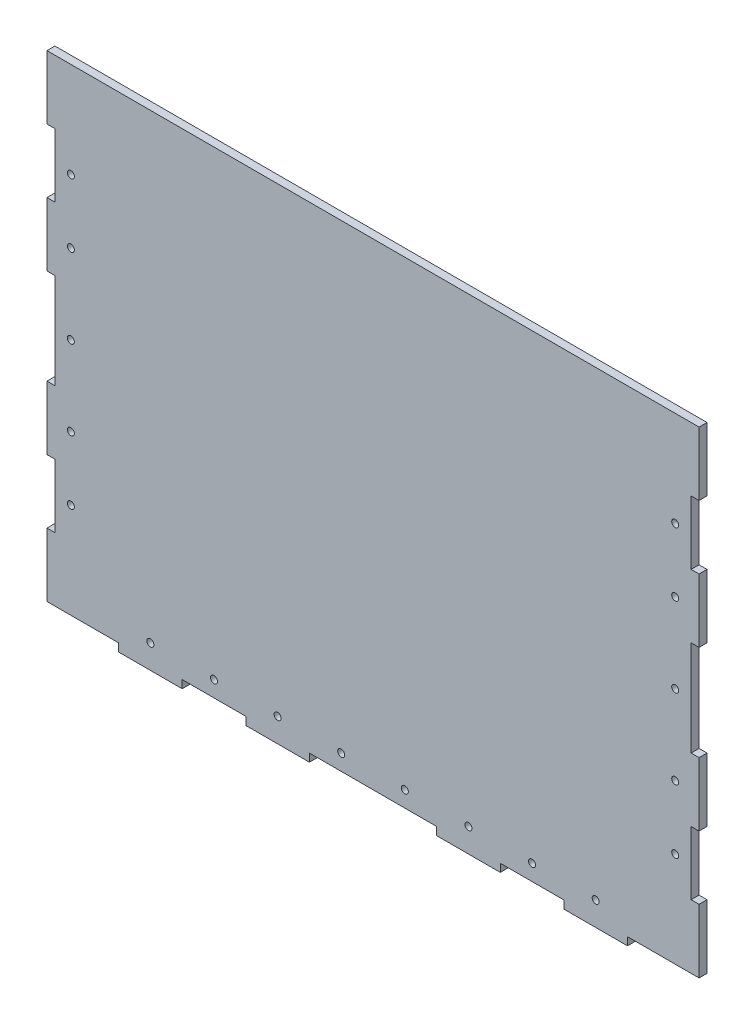
SolidWorks part; units mm, degrees
ref_plane "前视基准面" through (0, 0, 0) normal (0, 0, 1) x (1, 0, 0)
ref_plane "上视基准面" through (0, 0, 0) normal (0, 1, 0) x (1, 0, 0)
ref_plane "右视基准面" through (0, 0, 0) normal (1, 0, 0) x (0, 0, -1)
sketch "草图1" plane through (0, 0, 0) normal (0, 0, 1) x (1, 0, 0)
  line L2 (-200, 150) -> (200, 150)
  line L3 (200, -150) -> (200, -110)
  line L4 (-200, -150) -> (-200, -110)
  line L5 (-200, -150) -> (-160, -150)
  line L6 (-200, -150) -> (-160, -150)
  line L7 (-160, -150) -> (-160, -155)
  line L8 (-160, -155) -> (-120, -155)
  line L9 (-120, -155) -> (-120, -150)
  line L10 (-120, -150) -> (-80, -150)
  line L11 (-80, -150) -> (-80, -155)
  line L12 (-80, -155) -> (-40, -155)
  line L13 (-40, -155) -> (-40, -150)
  line L14 (-40, -150) -> (40, -150)
  line L15 (40, -150) -> (40, -155)
  line L16 (40, -155) -> (80, -155)
  line L17 (80, -155) -> (80, -150)
  line L18 (80, -150) -> (120, -150)
  line L19 (120, -150) -> (120, -155)
  line L20 (120, -155) -> (160, -155)
  line L21 (160, -155) -> (160, -150)
  line L22 (80, -150) -> (120, -150)
  line L23 (-120, -150) -> (-80, -150)
  line L24 (-40, -150) -> (40, -150)
  line L25 (160, -150) -> (200, -150)
  line L26 (-200, 110) -> (-200, 150)
  line L27 (-200, -70) -> (-200, -30)
  line L28 (-205, -30) -> (-205, 30)
  line L29 (-205, 30) -> (-200, 30)
  line L30 (-200, 30) -> (-200, 70)
  line L31 (-200, 70) -> (-205, 70)
  line L32 (-205, 70) -> (-205, 110)
  line L33 (-205, 110) -> (-200, 110)
  line L34 (-205, -30) -> (-200, -30)
  line L35 (-200, -70) -> (-205, -70)
  line L36 (-205, -70) -> (-205, -110)
  line L37 (-205, -110) -> (-200, -110)
  line L38 (-200, 30) -> (-200, 70)
  line L39 (200, 110) -> (200, 150)
  line L40 (205, -70) -> (205, -110)
  line L41 (205, -110) -> (200, -110)
  line L42 (200, -70) -> (205, -70)
  line L43 (205, -30) -> (200, -30)
  line L44 (205, -30) -> (205, 30)
  line L45 (205, 30) -> (200, 30)
  line L46 (200, 70) -> (205, 70)
  line L47 (205, 70) -> (205, 110)
  line L48 (205, 110) -> (200, 110)
  line L49 (200, 30) -> (200, 70)
  line L50 (200, -70) -> (200, -30)
  circle A0 centre (-140, -140) radius 2.2
  circle A1 centre (-100, -140) radius 2.2
  circle A2 centre (-60, -140) radius 2.2
  circle A3 centre (-20, -140) radius 2.2
  circle A4 centre (20, -140) radius 2.2
  circle A5 centre (60, -140) radius 2.2
  circle A6 centre (100, -140) radius 2.2
  circle A7 centre (140, -140) radius 2.2
  circle A8 centre (-190, 110) radius 2.2
  circle A9 centre (-190, 70) radius 2.2
  circle A10 centre (-190, 30) radius 2.2
  circle A11 centre (-190, -30) radius 2.2
  circle A12 centre (-190, -70) radius 2.2
  circle A13 centre (-190, -110) radius 2.2
  circle A14 centre (190, -110) radius 2.2
  circle A15 centre (190, -70) radius 2.2
  circle A16 centre (190, -30) radius 2.2
  circle A17 centre (190, 30) radius 2.2
  circle A18 centre (190, 70) radius 2.2
  circle A19 centre (190, 110) radius 2.2
extrude "凸台-拉伸1" add sketch "草图1" along normal blind 5 contours L42 L50 L43 L44 L45 L49 L46 L47 L48 L39 L2 L26 L33 L32 L31 L30 L29 L28 L34 L27 L35 L36 L37 L4 L5 L7 L8 L9 L10 L11 L12 L13 L14 L15 L16 L17 L18 L19 L20 L21 L25 L3 L41 L40 A18 A16 A14 region at (0, -0.8611, 0)
sketch "草图2" plane through (0, 0, 5) normal (0, 0, 1) x (1, 0, 0)
  line L0 (-205, 110) -> (-200, 110)
  line L1 (-205, 110) -> (-205, -110.2824)
  line L2 (-200, 110) -> (-200, -110.2824)
  line L3 (-205, -110.2824) -> (-200, -110.2824)
  line L4 (200, 110) -> (205, 110)
  line L5 (200, 110) -> (200, -109.8687)
  line L6 (205, 110) -> (205, -109.8687)
  line L7 (200, -109.8687) -> (205, -109.8687)
extrude "切除-拉伸1" cut sketch "草图2" against normal blind 10
sketch "草图3" plane through (0, 0, 5) normal (0, 0, 1) x (1, 0, 0)
  line L0 (-200, 150) -> (-205, 150)
  line L1 (-205, 150) -> (-205, 110)
  line L2 (-205, 110) -> (-200, 110)
  line L3 (-200, -150) -> (-200, 150) construction
  line L4 (-200, 30) -> (-200, 70)
  line L5 (-200, 70) -> (-205, 70)
  line L6 (-205, 70) -> (-205, 30)
  line L7 (-205, 30) -> (-200, 30)
  line L9 (-200, -30) -> (-205, -30)
  line L10 (-205, -30) -> (-205, -70)
  line L11 (-205, -70) -> (-200, -70)
  line L13 (-200, -110) -> (-205, -110)
  line L14 (-205, -110) -> (-205, -150)
  line L15 (-205, -150) -> (-200, -150)
  line L16 (-200, -70) -> (-200, -30)
  line L19 (205, -150) -> (200, -150)
  line L20 (205, -110) -> (205, -150)
  line L21 (200, -110) -> (205, -110)
  line L23 (205, -70) -> (200, -70)
  line L24 (205, -30) -> (205, -70)
  line L25 (200, -30) -> (205, -30)
  line L27 (205, 30) -> (200, 30)
  line L28 (205, 70) -> (205, 30)
  line L29 (200, 70) -> (205, 70)
  line L31 (205, 110) -> (200, 110)
  line L32 (205, 150) -> (205, 110)
  line L33 (200, 150) -> (205, 150)
  line L34 (-200, -150) -> (-200, -110)
  line L35 (200, 150) -> (200, 110)
  line L36 (-200, 110) -> (-200, 150)
  line L37 (200, 70) -> (200, 30)
  line L38 (200, -30) -> (200, -70)
  line L39 (200, -110) -> (200, -150)
extrude "凸台-拉伸3" add sketch "草图3" against normal blind 5
sketch "草图4" plane through (0, 0, 5) normal (0, 0, 1) x (1, 0, 0)
  line L0 (-193.4037, 139.8055) -> (197.0175, 139.8055)
  line L1 (-193.4037, 139.8055) -> (-193.4037, -124.8847)
  line L2 (197.0175, 139.8055) -> (197.0175, -124.8847)
  line L3 (-193.4037, -124.8847) -> (197.0175, -124.8847)
extrude "凸台-拉伸4" add sketch "草图4" against normal blind 5
sketch "草图5" plane through (0, 0, 5) normal (0, 0, 1) x (1, 0, 0)
  circle A11 centre (-190, 90) radius 2.2
  circle A12 centre (-190, 50) radius 2.2
  circle A13 centre (-190, 0) radius 2.2
  circle A14 centre (-190, -50) radius 2.2
  circle A15 centre (-190, -90) radius 2.2
  circle A16 centre (190, -90) radius 2.2
  circle A17 centre (190, -50) radius 2.2
  circle A18 centre (190, 0) radius 2.2
  circle A19 centre (190, 50) radius 2.2
  circle A20 centre (190, 90) radius 2.2
extrude "切除-拉伸2" cut sketch "草图5" against normal blind 5
